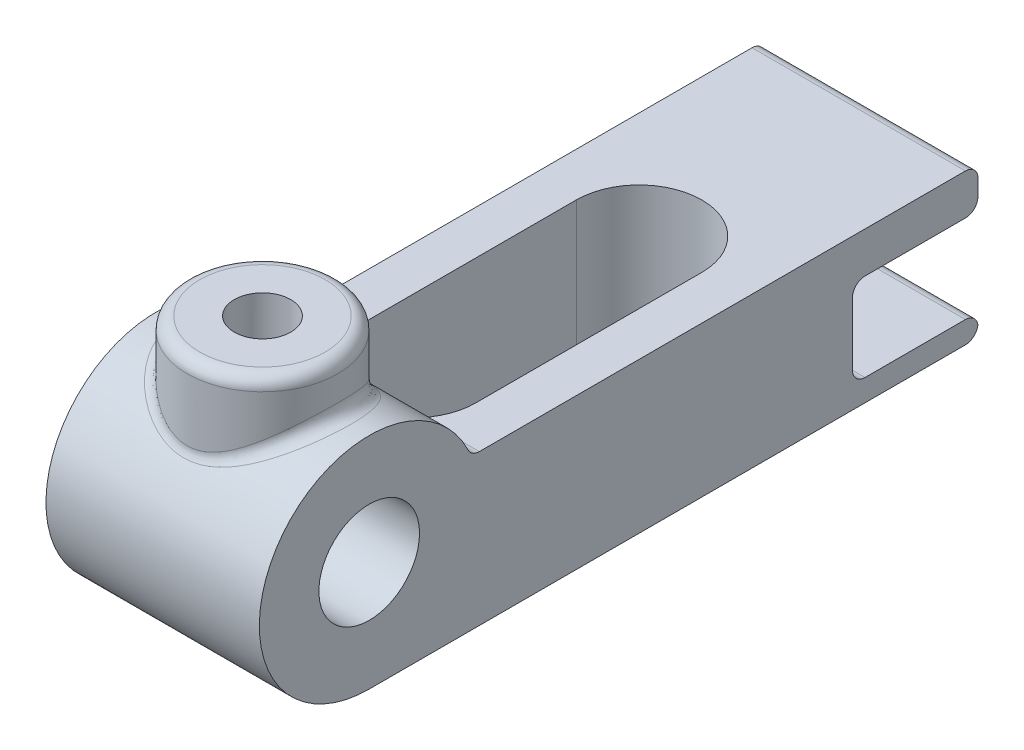
SolidWorks part; units mm, degrees
ref_plane "Front Plane" through (0, 0, 0) normal (0, 0, 1) x (1, 0, 0)
ref_plane "Top Plane" through (0, 0, 0) normal (0, 1, 0) x (1, 0, 0)
ref_plane "Right Plane" through (0, 0, 0) normal (1, 0, 0) x (0, 0, -1)
sketch "Sketch1" plane through (0, 0, 0) normal (1, 0, 0) x (0, 0, -1)
  line L0 (75.4062, 5.1594) -> (12.8969, 5.1594)
  line L1 (0, -13.8906) -> (75.4062, -13.8906)
  line L2 (76.9938, -12.3031) -> (76.9938, -12.7)
  line L3 (75.4062, -11.1125) -> (62.7063, -11.1125)
  line L4 (61.1187, -9.525) -> (61.1187, -1.5875)
  line L5 (62.7063, 0) -> (75.4062, 0)
  line L6 (76.9938, 1.5875) -> (76.9938, 3.5719)
  line L7 (61.1187, -5.5562) -> (76.9938, -5.5562) construction
  line L8 (37.7031, -13.8906) -> (37.7031, 5.1594) construction
  arc A0 (12.8969, 5.1594) -> (0, -13.8906) centre (0, 0) ccw
  circle A1 centre (0, 0) radius 6.3627
  arc A4 (76.9938, -12.7) -> (75.4062, -11.1125) centre (75.4062, -12.7) ccw
  arc A5 (62.7063, -11.1125) -> (61.1187, -9.525) centre (62.7063, -9.525) cw
  arc A6 (61.1187, -1.5875) -> (62.7063, 0) centre (62.7063, -1.5875) cw
  arc A7 (75.4062, 0) -> (76.9938, 1.5875) centre (75.4062, 1.5875) ccw
  arc A8 (75.4062, 5.1594) -> (76.9938, 3.5719) centre (75.4062, 3.5719) cw
  arc A9 (75.4062, -13.8906) -> (76.9938, -12.3031) centre (75.4062, -12.3031) ccw
  point P13 (0, 0)
  point P28 (76.9938, 5.1594)
  point P31 (76.9938, -13.8906)
  dimension "D1" = 27.7812
  dimension "D2" = 12.7254
  dimension "D3" = 19.05
  dimension "D4" = 11.1125
  dimension "D7" = 1.5875
  dimension "D8" = 1.5875
  dimension "D9" = 1.5875
  dimension "D10" = 1.5875
  dimension "D11" = 5.5562
  dimension "D5" = 76.9938
  dimension "D6" = 15.875
extrude "Boss-Extrude1" add sketch "Sketch1" along normal mid plane 26.9875 contours L1 A9 A4 L3 A5 L4 A6 L5 A7 L6 A8 L0 A0 A1 region at (0, -3.0408, -27.6814)
sketch "Sketch2" plane through (0, 5.1594, 0) normal (0, 1, 0) x (1, 0, 0)
  line L0 (0, 12.8969) -> (0, 75.4062) construction
  line L1 (13.4937, 12.8969) -> (-13.4937, 12.8969) construction
  line L2 (13.4937, 75.4062) -> (-13.4937, 75.4062) construction
  line L3 (0, 47.625) -> (0, 19.05) construction
  line L4 (7.9375, 47.625) -> (7.9375, 19.05)
  line L5 (-7.9375, 47.625) -> (-7.9375, 19.05)
  arc A0 (7.9375, 47.625) -> (-7.9375, 47.625) centre (0, 47.625) ccw
  arc A1 (-7.9375, 19.05) -> (7.9375, 19.05) centre (0, 19.05) ccw
  point P8 (0, 33.3375)
  dimension "D1" = 19.05
  dimension "D2" = 28.575
  dimension "D3" = 15.875
extrude "Cut-Extrude1" cut sketch "Sketch2" against normal through all both and the other way through all
ref_plane "Plane1" through (0, 20.2406, 0) normal (0, 1, 0) x (1, 0, 0)
sketch "Sketch3" plane through (0, 20.2406, 0) normal (0, 1, 0) x (1, 0, 0)
  circle A0 centre (0, 0) radius 9.525
  circle A1 centre (0, 0) radius 3.5719
  dimension "D1" = 19.05
  dimension "D2" = 7.1437
extrude "Boss-Extrude2" add sketch "Sketch3" against normal up to surface (10.13 mm away) up to face at (0.0792, 3.3863, -2.3192)
extrude "Cut-Extrude2" cut sketch "Sketch3<2>" against normal up to surface (14.9751 mm away) contours A1 region at (0, 20.2406, 0) up to face at (13.4937, 0, -6.3627)
sketch "Sketch3<2>" plane through (0, 20.2406, 0) normal (0, 1, 0) x (1, 0, 0) same geometry as "Sketch3"
fillet "Fillet1" radius 1.5875 4 edges at (0, 20.2406, 9.525) (-9.254, 5.1594, -12.8969) (9.254, 5.1594, -12.8969) (-1.3413, 10.1992, -9.4301)
